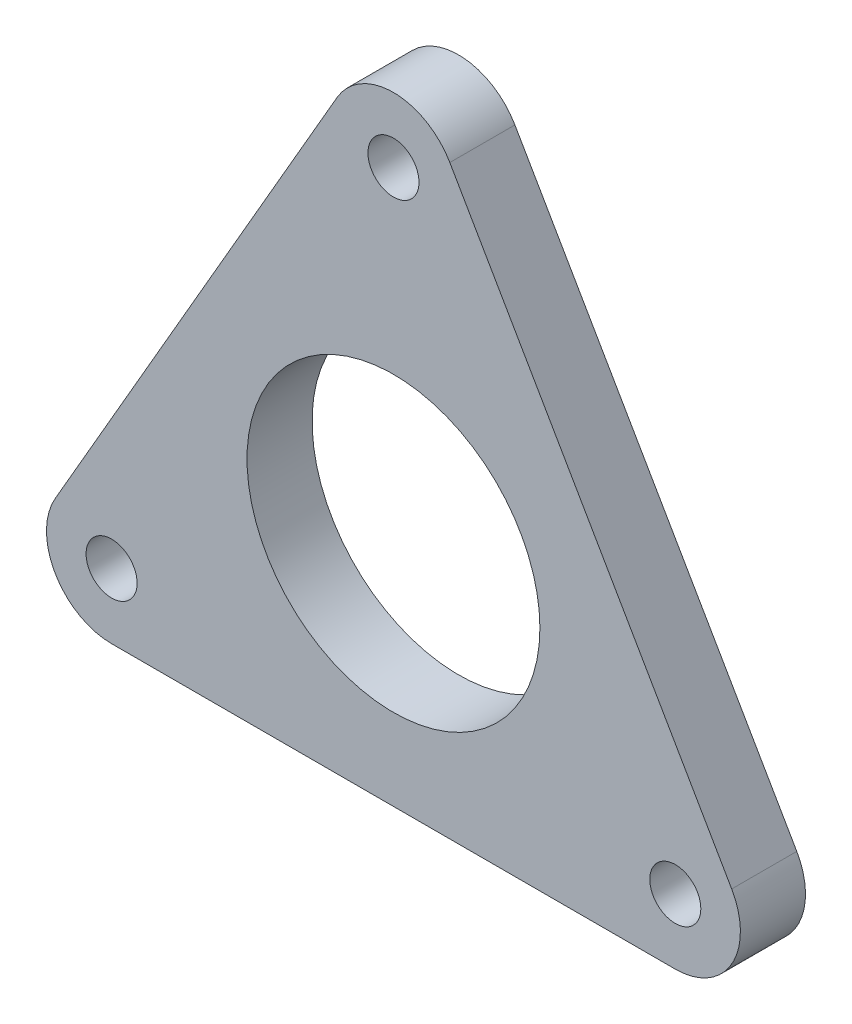
SolidWorks part; units mm, degrees
material "6061-T6 (SS)"
ref_plane "Front Plane" through (0, 0, 0) normal (0, 0, 1) x (1, 0, 0)
ref_plane "Top Plane" through (0, 0, 0) normal (0, 1, 0) x (1, 0, 0)
ref_plane "Right Plane" through (0, 0, 0) normal (1, 0, 0) x (0, 0, -1)
sketch "Sketch2" plane through (0, 0, 0) normal (0, 0, 1) x (1, 0, 0)
  line L0 (0, 44.45) -> (38.4948, -22.225)
  line L1 (38.4948, -22.225) -> (-38.4948, -22.225)
  line L2 (-38.4948, -22.225) -> (0, 44.45)
  line L3 (-32.8175, -12.3915) -> (-15.3289, 11.3105) construction
  line L4 (-27.1401, -22.225) -> (2.1307, -18.9305) construction
  line L5 (-5.6774, 34.6165) -> (-17.4596, 7.62) construction
  line L6 (5.6774, 34.6165) -> (17.4596, 7.62) construction
  line L7 (32.8175, -12.3915) -> (15.3289, 11.3105) construction
  line L8 (27.1401, -22.225) -> (-2.1307, -18.9305) construction
  circle A0 centre (0, 0) radius 14.2875
  circle A1 centre (0, 31.75) radius 2.4892
  circle A2 centre (27.4963, -15.875) radius 2.4892
  circle A3 centre (-27.4963, -15.875) radius 2.4892
  circle A4 centre (27.4963, -15.875) radius 6.35 construction
  circle A5 centre (0, 31.75) radius 6.35 construction
  circle A6 centre (-27.4963, -15.875) radius 6.35 construction
  circle A7 centre (0, 0) radius 19.05 construction
  point P11 (0, 0)
  point P16 (0, -22.225)
  point P33 (0, 0)
  dimension "D1" = 28.575
  dimension "D2" = 4.9784
  dimension "D6" = 12.7
  dimension "D5" = 38.1
  dimension "D3" = 31.75
  dimension "D4" = 3
  dimension "D7" = 3
extrude "Boss-Extrude1" add sketch "Sketch2" along normal blind 6.35 contours A7 A0 | A7 L4 L8 A4 L7 L6 | A7 L7 L6 A5 L5 L3 | A7 L5 L3 A6 L4 L8 | A6 A3 | A4 A2 | A5 A1 | A7 L3 L5 | A7 L6 L7 | A7 L8 L4 region at (18.3654, 10.6033, 0)
fillet "Fillet1" radius 6.35 3 edges at (38.4948, -22.225, 3.175) (-38.4948, -22.225, 3.175) (0, 44.45, 3.175)
